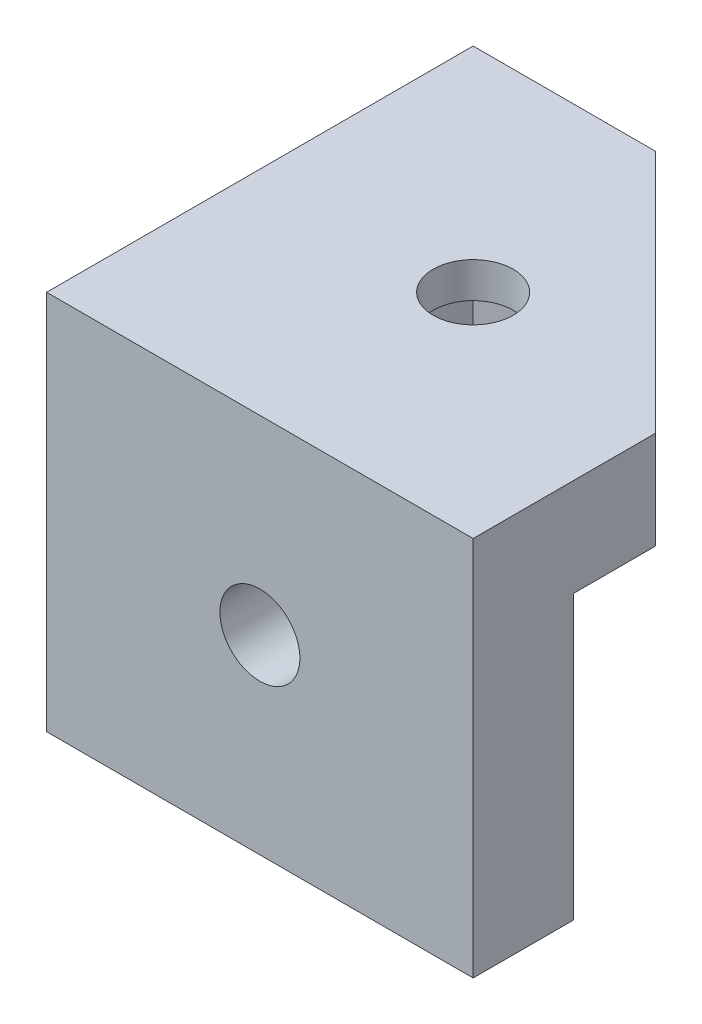
SolidWorks part; units mm, degrees
ref_plane "Front Plane" through (0, 0, 0) normal (0, 0, 1) x (1, 0, 0)
ref_plane "Top Plane" through (0, 0, 0) normal (0, 1, 0) x (1, 0, 0)
ref_plane "Right Plane" through (0, 0, 0) normal (1, 0, 0) x (0, 0, -1)
sketch "Sketch1" plane through (0, 0, 0) normal (0, 1, 0) x (1, 0, 0)
  line L1 (0, 0) -> (38.1, 0)
  line L5 (0, 0) -> (0, 38.1)
  line L6 (0, 38.1) -> (38.1, 38.1)
  line L8 (38.1, 38.1) -> (38.1, 0)
  dimension "D1" = 38.1
extrude "Main Body" add sketch "Sketch1" along normal blind 34
sketch "Sketch3" plane through (0, 0, 0) normal (0, 0, 1) x (1, 0, 0)
  line L0 (0, 0) -> (38.1, 34) construction
  circle A0 centre (19.05, 17) radius 3.5719
  circle A1 centre (19.05, 17) radius 7.9375 construction
  dimension "D1" = 7.1437
  dimension "D2" = 15.875
extrude "9/32 Right Rail" cut sketch "Sketch3" against normal blind 5.5562 and the other way through all
sketch "Sketch4" plane through (0, 0, 0) normal (-1, 0, 0) x (0, 0, 1)
  line L0 (0, 0) -> (-38.1, 34) construction
  circle A0 centre (-19.05, 17) radius 3.5719
  circle A1 centre (-19.05, 17) radius 7.9375 construction
  dimension "D1" = 7.1437
  dimension "D2" = 15.875
extrude "9/32 Left Rail" cut sketch "Sketch4" against normal blind 5.5562
sketch "Sketch8" plane through (0, 34, 0) normal (0, 1, 0) x (1, 0, 0)
  line L0 (0, 0) -> (38.1, 38.1) construction
  circle A0 centre (19.05, 19.05) radius 3.175 construction
  circle A1 centre (19.05, 19.05) radius 7.9375 construction
  circle A2 centre (19.05, 19.05) radius 3.5719
  dimension "D1" = 6.35
  dimension "D2" = 15.875
  dimension "D3" = 0.3969
extrude "9/32 Topper" cut sketch "Sketch8" against normal blind 10 and the other way through all
ref_plane "Plane1" through (5.5562, 0, 0) normal (-1, 0, 0) x (0, 0, 1)
sketch "Sketch9" plane through (0, 0, 0) normal (-1, 0, 0) x (0, 0, 1)
  line L0 (-19.05, 0) -> (-19.05, 34) construction
  line L1 (-12.6342, 17) -> (-15.8421, 22.5562) construction
  line L2 (-15.8421, 22.5562) -> (-22.2579, 22.5562) construction
  line L3 (-22.2579, 22.5562) -> (-25.4658, 17) construction
  line L4 (-25.4658, 17) -> (-22.2579, 11.4437) construction
  line L5 (-22.2579, 11.4437) -> (-15.8421, 11.4437) construction
  line L6 (-15.8421, 11.4437) -> (-12.6342, 17) construction
  line L7 (-38.1, 0) -> (0, 0) construction
  line L8 (-38.1, 34) -> (0, 34) construction
  line L9 (-22.3725, 22.7547) -> (-25.6949, 17)
  line L10 (-25.6949, 17) -> (-22.3725, 11.2453)
  line L11 (-22.3725, 11.2453) -> (-15.7275, 11.2453)
  line L12 (-15.7275, 11.2453) -> (-12.4051, 17)
  line L13 (-12.4051, 17) -> (-15.7275, 22.7547)
  line L14 (-15.7275, 22.7547) -> (-22.3725, 22.7547)
  line L15 (-38.1, 27.65) -> (-38.1, 6.35) construction
  line L16 (-38.1, 34) -> (-38.1, 0) construction
  line L17 (-38.1, 6.35) -> (-5.5562, 6.35) construction
  line L18 (-5.5562, 6.35) -> (-5.5562, 27.65) construction
  line L19 (-5.5562, 27.65) -> (-38.1, 27.65) construction
  line L20 (0, 34) -> (0, 0) construction
  circle A0 centre (-19.05, 17) radius 5.5563 construction
  point P15 (-19.05, 17)
  point P27 (-38.1, 17)
  point P29 (-38.1, 17)
  dimension "D1" = 11.1125
  dimension "D3" = 5.5562
  dimension "D4" = 6.35
  dimension "D2" = 0.1984
extrude "Cut-Extrude3" cut sketch "Sketch9" against normal up to surface (38.1 mm away) from surface up to face at (38.1, 17, -19.05) starting at plane "Plane1"
ref_plane "Plane2" through (0, 0, -5.5563) normal (0, 0, 1) x (1, 0, 0)
sketch "Sketch10" plane through (0, 0, 0) normal (0, 0, 1) x (1, 0, 0)
  line L0 (19.05, 0) -> (19.05, 34) construction
  line L1 (0, 0) -> (38.1, 0) construction
  line L2 (0, 34) -> (38.1, 34) construction
  line L3 (15.7275, 22.7547) -> (12.4051, 17)
  line L4 (25.4658, 17) -> (22.2579, 22.5562) construction
  line L5 (22.2579, 22.5562) -> (15.8421, 22.5562) construction
  line L6 (15.8421, 22.5562) -> (12.6342, 17) construction
  line L13 (12.6342, 17) -> (15.8421, 11.4437) construction
  line L14 (15.8421, 11.4437) -> (22.2579, 11.4437) construction
  line L15 (22.2579, 11.4437) -> (25.4658, 17) construction
  line L16 (12.4051, 17) -> (15.7275, 11.2453)
  line L17 (15.7275, 11.2453) -> (22.3725, 11.2453)
  line L18 (22.3725, 11.2453) -> (25.6949, 17)
  line L19 (25.6949, 17) -> (22.3725, 22.7547)
  line L20 (22.3725, 22.7547) -> (15.7275, 22.7547)
  circle A0 centre (19.05, 17) radius 5.5563 construction
  dimension "D1" = 11.1125
  dimension "D2" = 0.1984
extrude "Cut-Extrude4" cut sketch "Sketch10" against normal up to surface (38.1 mm away) from surface up to face at (19.05, 17, -38.1) starting at plane "Plane2"
sketch "Sketch13" plane through (0, 34, 0) normal (0, 1, 0) x (1, 0, 0)
  line L2 (38.1, 8.9807) -> (8.9807, 8.9807)
  line L3 (8.9807, 38.1) -> (8.9807, 8.9807)
  line L7 (38.1, 38.1) -> (0, 38.1) construction
  line L8 (38.1, 0) -> (38.1, 38.1) construction
  line L9 (8.9807, 38.1) -> (38.1, 38.1)
  line L10 (38.1, 38.1) -> (38.1, 8.9807)
  line L11 (12.4051, 12.4051) -> (12.4051, 5.5563) construction
  line L12 (12.4051, 12.4051) -> (5.5562, 12.4051) construction
  line L13 (12.4051, 12.4051) -> (12.4051, 5.5563) construction
  line L14 (12.4051, 12.4051) -> (5.5562, 12.4051) construction
  point P10 (12.4051, 8.9807)
ref_plane "Plane4" through (0, 17, 0) normal (0, 1, 0) x (1, 0, 0)
extrude "Cut-Extrude12" cut sketch "Sketch13" along direction (0, -1, 0) on the side of the normal offset from surface 8.7312 and the other way offset from surface 3.175 from surface up to face at (19.05, 34, -22.6219) other way up to face at (19.05, 0, -19.05) starting at plane "Plane4"
sketch "Sketch14" plane through (0, 34, 0) normal (0, 1, 0) x (1, 0, 0)
  line L0 (38.1, 0) -> (0, 38.1) construction
  line L1 (23.7487, 14.3513) -> (25.4685, 20.7698)
  line L2 (23.5867, 14.5133) -> (25.2472, 20.7105) construction
  line L3 (25.2472, 20.7105) -> (20.7105, 25.2472) construction
  line L4 (20.7105, 25.2472) -> (14.5133, 23.5867) construction
  line L5 (14.5133, 23.5867) -> (12.8528, 17.3895) construction
  line L6 (12.8528, 17.3895) -> (17.3895, 12.8528) construction
  line L7 (17.3895, 12.8528) -> (23.5867, 14.5133) construction
  line L8 (25.4685, 20.7698) -> (20.7698, 25.4685)
  line L9 (20.7698, 25.4685) -> (14.3513, 23.7487)
  line L10 (14.3513, 23.7487) -> (12.6315, 17.3302)
  line L11 (12.6315, 17.3302) -> (17.3302, 12.6315)
  line L12 (17.3302, 12.6315) -> (23.7487, 14.3513)
  circle A0 centre (19.05, 19.05) radius 5.5562 construction
  dimension "D1" = 11.1125
  dimension "D2" = 0.1984
extrude "Cut-Extrude15" cut sketch "Sketch14" along normal offset from surface (13.825 mm away) 3.175 from surface up to face at (19.05, 34, -22.6219) starting at plane "Plane4"
sketch "Sketch15" plane through (0, 0, 0) normal (0, -1, 0) x (1, 0, 0)
  line L0 (38.1, -8.9807) -> (8.9807, -38.1)
  line L4 (38.1, -38.1) -> (38.1, -8.9807)
  line L5 (8.9807, -38.1) -> (38.1, -38.1)
  line L6 (8.9807, -8.9807) -> (8.9807, -38.1)
  line L7 (38.1, -8.9807) -> (8.9807, -8.9807)
  line L8 (38.1, -38.1) -> (38.1, -8.9807)
  line L9 (8.9807, -38.1) -> (38.1, -38.1)
  line L10 (8.9807, -8.9807) -> (8.9807, -38.1) construction
  line L11 (38.1, -8.9807) -> (8.9807, -8.9807) construction
  dimension "D1" = 0
extrude "Cut-Extrude16" cut sketch "Sketch15" against normal up to next
sketch "Sketch16" plane through (0, 34, 0) normal (0, 1, 0) x (1, 0, 0)
  line L0 (38.1, 38.1) -> (16.2767, 38.1)
  line L1 (38.1, 38.1) -> (0, 38.1) construction
  line L2 (16.2767, 38.1) -> (38.1, 16.2767)
  line L3 (38.1, 16.2767) -> (38.1, 38.1)
  line L4 (38.1, 0) -> (38.1, 38.1) construction
  circle A2 centre (19.05, 19.05) radius 3.5719 construction
  dimension "D1" = 7.9375
extrude "Cut-Extrude17" cut sketch "Sketch16" against normal up to next
